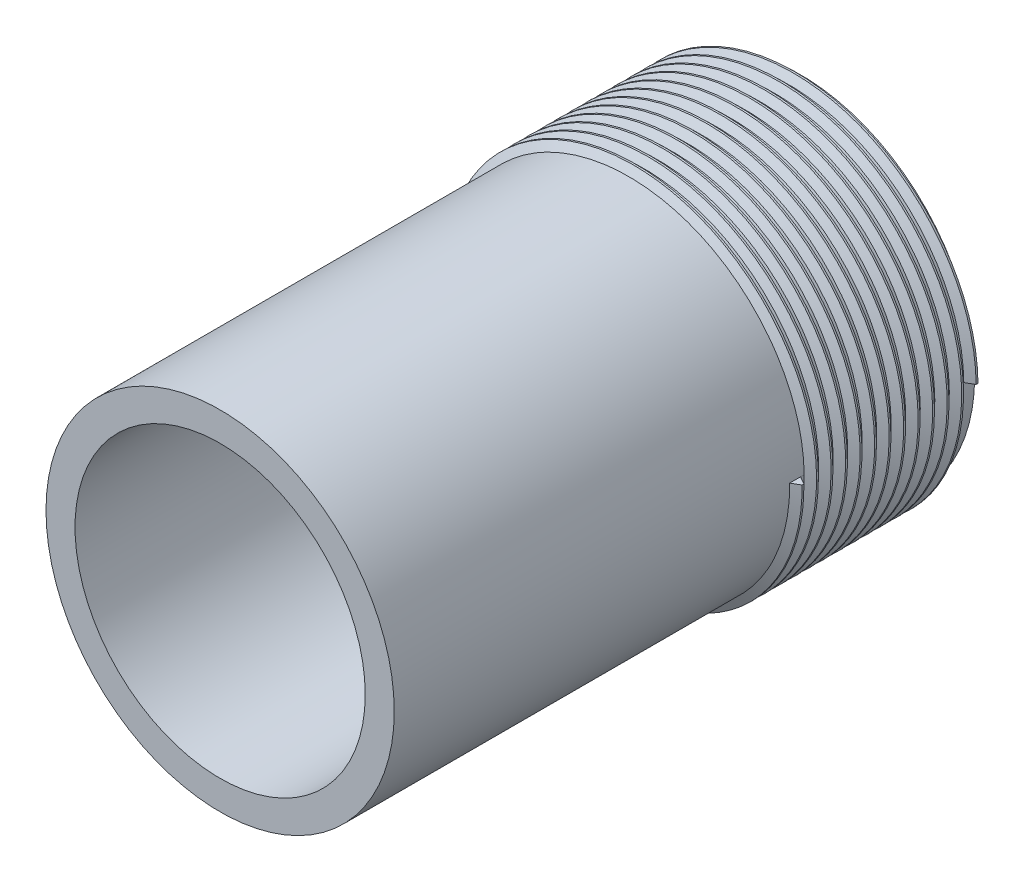
SolidWorks part; units mm, degrees
material "AISI Type 316L stainless steel"
ref_plane "Front Plane" through (0, 0, 0) normal (0, 0, 1) x (1, 0, 0)
ref_plane "Top Plane" through (0, 0, 0) normal (0, 1, 0) x (1, 0, 0)
ref_plane "Right Plane" through (0, 0, 0) normal (1, 0, 0) x (0, 0, -1)
sketch "Sketch1" plane through (0, 0, 0) normal (0, 0, 1) x (1, 0, 0)
  circle A0 centre (0, 0) radius 2.5
  circle A1 centre (0, 0) radius 3
  dimension "D1" = 6
  dimension "D2" = 5
extrude "Boss-Extrude1" add sketch "Sketch1" along normal mid plane 10
thread "Thread1" pitch 0.25 method extrude profile "Thread Profile1" start angle 0, offset 0, length 3, pitch 0.25, diameter 6
ref_plane "Plane1" through (3, 0, -5) normal (0, -1, 0) x (1, 0, 0)
sketch "Thread Profile1" plane through (3, 0, -5) normal (0, -1, 0) x (1, 0, 0)
  line L0 (0, 0) -> (0, 0.25) construction
  line L1 (0, 0) -> (0.1353, 0.0781)
  line L2 (0.1353, 0.0781) -> (0.1353, 0.1094)
  line L3 (0.1353, 0.1094) -> (0, 0.1875)
  line L4 (0.1353, 0.0937) -> (0, 0.0937) construction
  line L11 (0, 0) -> (0, 0.1875)
  point P2 (0, 0)
  dimension "Pitch" = 0.25
  dimension "Profile_Angle" = 60
  dimension "Profile_Land" = 0.0312
  dimension "Profile_Height" = 0.1353
